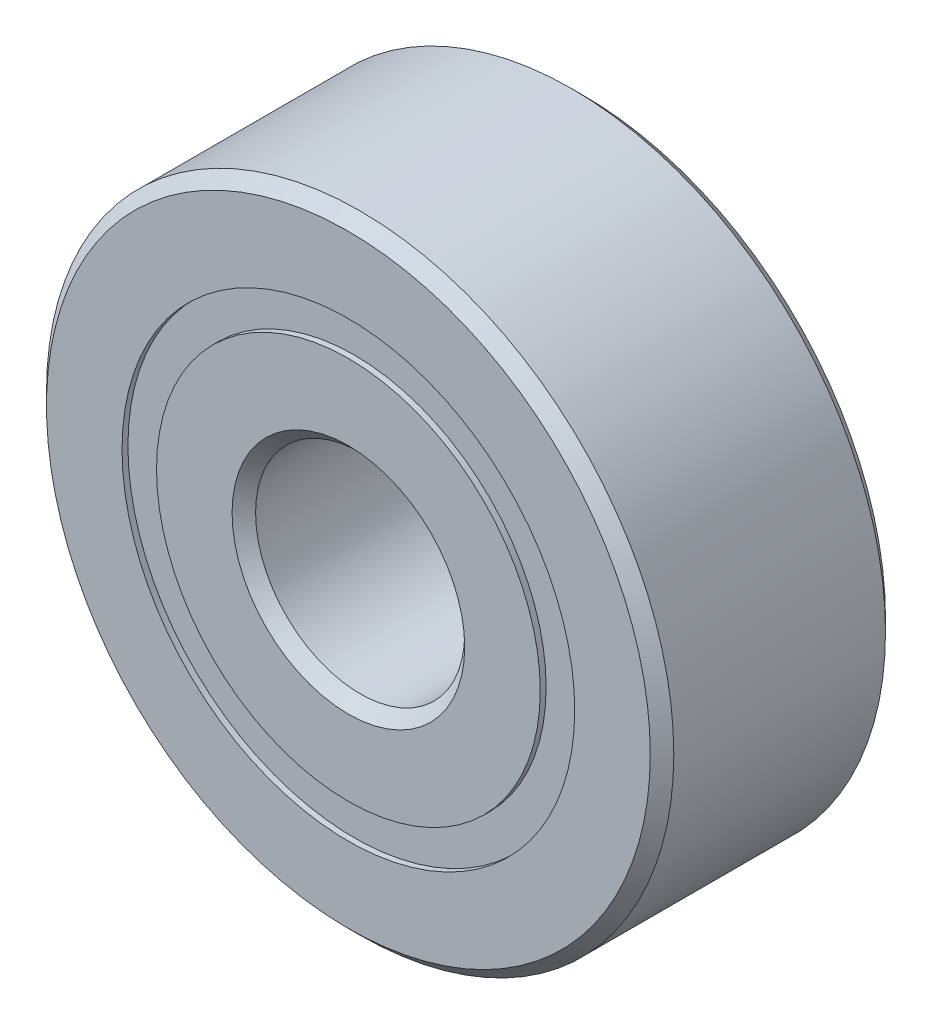
SolidWorks part; units mm, degrees
material "AISI 304"
ref_plane "Front Plane" through (0, 0, 0) normal (0, 0, 1) x (1, 0, 0)
ref_plane "Top Plane" through (0, 0, 0) normal (0, 1, 0) x (1, 0, 0)
ref_plane "Right Plane" through (0, 0, 0) normal (1, 0, 0) x (0, 0, -1)
sketch "Sketch1" plane through (0, 0, 0) normal (1, 0, 0) x (0, 0, -1)
  line L0 (-3.5719, 0) -> (3.5719, 0) construction
  line L1 (0, 9.525) -> (0, -9.525) construction
  line L2 (3.2147, 9.525) -> (-3.2147, 9.525)
  line L3 (-3.2147, 9.525) -> (-3.5719, 9.1678)
  line L4 (-3.5719, 9.1678) -> (-3.5719, 6.8734)
  line L5 (-3.5719, 6.8734) -> (-1.5875, 6.8734)
  line L6 (3.5719, 6.8734) -> (1.5875, 6.8734)
  line L7 (3.5719, 9.1678) -> (3.5719, 6.8734)
  line L8 (3.2147, 9.525) -> (3.5719, 9.1678)
  line L9 (0, 9.525) -> (0, 6.35) construction
  line L10 (0, 6.35) -> (0, 3.175) construction
  arc A0 (-1.5875, 6.8734) -> (1.5875, 6.8734) centre (0, 6.35) cw
  point P14 (0, 3.175)
  dimension "D3" = 3.175
  dimension "D1" = 45
  dimension "Width" = 7.1437
  dimension "OD" = 19.05
  dimension "D2" = 0.3572
  dimension "Shaft Dia" = 6.35
  dimension "D4" = 0.5234
revolve "Revolve1" add sketch "Sketch1" angle 360 about L0
sketch "Sketch3" plane through (0, 0, 0) normal (1, 0, 0) x (0, 0, -1)
  line L0 (-3.5719, 5.8266) -> (-1.5875, 5.8266)
  line L1 (0, 9.525) -> (0, -9.525) construction
  line L2 (-3.5719, 9.1678) -> (-3.5719, 6.8734) construction
  line L3 (-3.5719, 5.8266) -> (-3.5719, 3.5322)
  line L4 (-3.2147, 9.525) -> (-3.5719, 9.1678) construction
  line L5 (-3.5719, 3.5322) -> (-3.2147, 3.175)
  line L6 (-3.2147, 3.175) -> (3.2147, 3.175)
  line L7 (3.2147, 9.525) -> (3.2147, -9.525) construction
  line L8 (3.2147, 3.175) -> (3.5719, 3.5322)
  line L9 (3.5719, -9.1678) -> (3.5719, 9.1678) construction
  line L10 (3.5719, 3.5322) -> (3.5719, 5.8266)
  line L11 (3.5719, 5.8266) -> (1.5875, 5.8266)
  line L13 (3.2147, 9.525) -> (3.5719, 9.1678) construction
  arc A0 (1.5875, 6.8734) -> (-1.5875, 6.8734) centre (0, 6.35) ccw construction
  arc A1 (1.5875, 5.8266) -> (-1.5875, 5.8266) centre (0, 6.35) cw
revolve "Revolve3" add sketch "Sketch3" angle 360 about L0
sketch "Sketch4" plane through (0, 0, 0) normal (1, 0, 0) x (0, 0, -1)
  line L0 (-1.6715, 6.35) -> (1.6715, 6.35)
  arc A2 (-1.6715, 6.35) -> (1.6715, 6.35) centre (0, 6.35) cw
  arc A3 (1.5875, 6.8734) -> (-1.5875, 6.8734) centre (0, 6.35) ccw construction
revolve "Revolve4" add sketch "Sketch4" angle 360 about L0
ref_axis "Axis1" through (0, 0, -3.5719) along (0, 0, 1)
pattern_circular "CirPattern1" count 10 every 36 about axis through (0, 0, -3.5719) along (0, 0, 1) of bodies 104
sketch "Sketch5" plane through (0, 0, 0) normal (1, 0, 0) x (0, 0, -1)
  line L0 (-3.5719, 6.8734) -> (-1.5875, 6.8734) construction
  line L1 (-3.3933, 6.8734) -> (-1.6715, 6.8734)
  line L2 (-3.3933, 6.8734) -> (-3.3933, 5.8266)
  line L3 (-3.3933, 5.8266) -> (-1.6715, 5.8266)
  line L4 (-1.6715, 6.8734) -> (-1.6715, 5.8266)
  line L5 (-3.5719, 5.8266) -> (-1.5875, 5.8266) construction
  line L6 (3.5719, 6.8734) -> (1.5875, 6.8734) construction
  line L7 (3.3933, 6.8734) -> (1.6715, 6.8734)
  line L8 (3.3933, 6.8734) -> (3.3933, 5.8266)
  line L9 (3.3933, 5.8266) -> (1.6715, 5.8266)
  line L10 (1.6715, 6.8734) -> (1.6715, 5.8266)
  line L11 (3.5719, 5.8266) -> (1.5875, 5.8266) construction
  line L12 (-3.2147, 9.525) -> (-3.5719, 9.1678) construction
  point P18 (-3.3933, 9.3464)
revolve "Revolve5" add sketch "Sketch5" angle 360 about L0
equation "\"D2@Sketch1\" = \"Width@Sketch1\"*.05"
equation "\"D3@Sketch1\" = \"Width@Sketch1\"/2.25"
equation "\"D4@Sketch1\" = (((\"OD@Sketch1\"-\"Width@Sketch1\")/2)/3.25)/3.5"
equation "\"D2@CirPattern1\" = 360/\"Balls@CirPattern1\""
